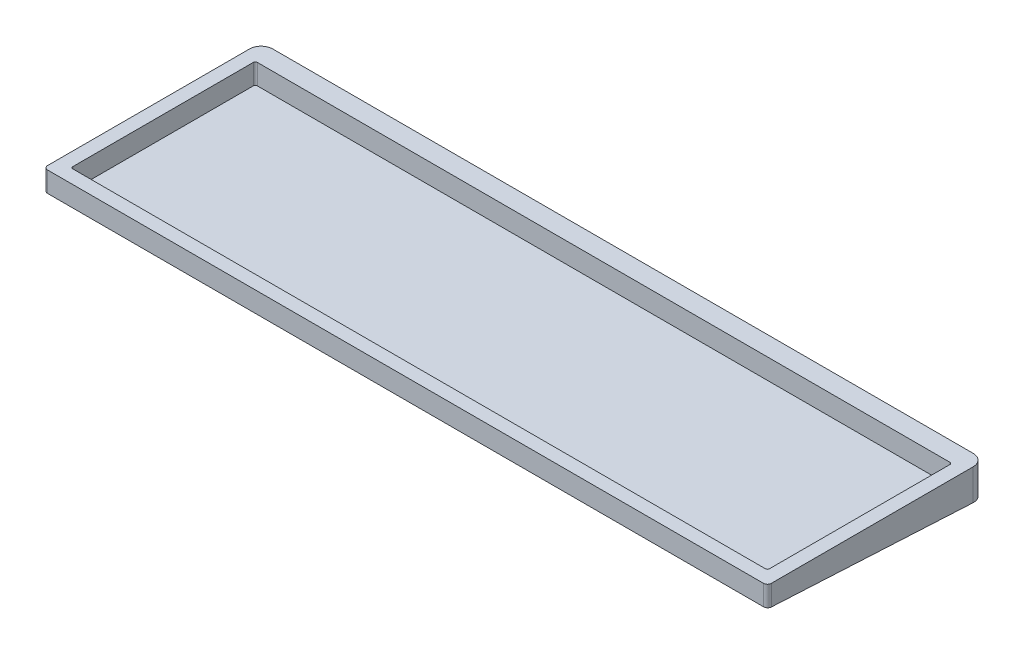
SolidWorks part; units mm, degrees
ref_plane "Front Plane" through (0, 0, 0) normal (0, 0, 1) x (1, 0, 0)
ref_plane "Top Plane" through (0, 0, 0) normal (0, 1, 0) x (1, 0, 0)
ref_plane "Right Plane" through (0, 0, 0) normal (1, 0, 0) x (0, 0, -1)
sketch "Sketch1" plane through (0, 0, 0) normal (0, 1, 0) x (1, 0, 0)
  line L1 (-178.825, 47.625) -> (178.825, 47.625)
  line L2 (-179.825, 46.625) -> (-179.825, -46.625)
  line L3 (-178.825, -47.625) -> (178.825, -47.625)
  line L4 (179.825, 46.625) -> (179.825, -46.625)
  line L5 (-179.825, 47.625) -> (179.825, -47.625) construction
  line L6 (-179.825, -47.625) -> (179.825, 47.625) construction
  arc A0 (178.825, -47.625) -> (179.825, -46.625) centre (178.825, -46.625) ccw
  arc A1 (178.825, 47.625) -> (179.825, 46.625) centre (178.825, 46.625) cw
  arc A2 (-179.825, -46.625) -> (-178.825, -47.625) centre (-178.825, -46.625) ccw
  arc A3 (-178.825, 47.625) -> (-179.825, 46.625) centre (-178.825, 46.625) ccw
  circle A4 centre (157.075, 19.175) radius 1.1
  circle A5 centre (136.925, -16.775) radius 1.1
  circle A6 centre (-153.475, 33.725) radius 1.1
  circle A7 centre (17.925, 22.275) radius 1.1
  circle A8 centre (17.875, -35.075) radius 1.1
  circle A9 centre (-130.375, -35.725) radius 1.1
  point P0 (0, 0)
  dimension "D3" = 1
  dimension "D4" = 2.2
  dimension "D7" = 2.2
  dimension "D8" = 2.2
  dimension "D9" = 2.2
  dimension "D10" = 2.2
  dimension "D11" = 2.2
  dimension "D1" = 359.65
  dimension "D2" = 95.25
  dimension "D5" = 22.75
  dimension "D6" = 28.45
  dimension "D12" = 42.9
  dimension "D13" = 30.85
  dimension "D14" = 25.35
  dimension "D15" = 161.9
  dimension "D16" = 12.55
  dimension "D17" = 161.95
  dimension "D18" = 11.9
  dimension "D19" = 49.45
  dimension "D20" = 13.9
  dimension "D21" = 26.35
sketch "Sketch2" plane through (0, 0, 0) normal (0, 1, 0) x (1, 0, 0)
  line L0 (-179.825, 46.625) -> (-179.825, -46.625) construction
  line L1 (-178.825, -47.625) -> (178.825, -47.625) construction
  line L2 (179.825, 46.625) -> (179.825, -46.625) construction
  line L3 (-178.825, 47.625) -> (178.825, 47.625) construction
  line L4 (-179.825, 46.625) -> (-179.825, -46.625)
  line L5 (-178.825, -47.625) -> (178.825, -47.625)
  line L6 (179.825, 46.625) -> (179.825, -46.625)
  line L7 (-178.825, 47.625) -> (178.825, 47.625)
  line L9 (-180.825, 57.625) -> (180.825, 57.625)
  line L10 (-186.825, 51.625) -> (-186.825, -52.625)
  line L11 (-184.825, -54.625) -> (184.825, -54.625)
  line L12 (186.825, 51.625) -> (186.825, -52.625)
  circle A0 centre (157.075, 19.175) radius 1.1 construction
  circle A1 centre (136.925, -16.775) radius 1.1 construction
  circle A2 centre (17.875, -35.075) radius 1.1 construction
  circle A3 centre (17.925, 22.275) radius 1.1 construction
  circle A4 centre (-153.475, 33.725) radius 1.1 construction
  circle A5 centre (-130.375, -35.725) radius 1.1 construction
  arc A6 (-179.825, -46.625) -> (-178.825, -47.625) centre (-178.825, -46.625) ccw construction
  arc A7 (178.825, -47.625) -> (179.825, -46.625) centre (178.825, -46.625) ccw construction
  arc A8 (179.825, 46.625) -> (178.825, 47.625) centre (178.825, 46.625) ccw construction
  arc A9 (-178.825, 47.625) -> (-179.825, 46.625) centre (-178.825, 46.625) ccw construction
  circle A10 centre (157.075, 19.175) radius 1.1
  circle A11 centre (136.925, -16.775) radius 1.1
  circle A12 centre (17.875, -35.075) radius 1.1
  circle A13 centre (17.925, 22.275) radius 1.1
  circle A14 centre (-153.475, 33.725) radius 1.1
  circle A15 centre (-130.375, -35.725) radius 1.1
  arc A16 (-179.825, -46.625) -> (-178.825, -47.625) centre (-178.825, -46.625) ccw
  arc A17 (178.825, -47.625) -> (179.825, -46.625) centre (178.825, -46.625) ccw
  arc A18 (179.825, 46.625) -> (178.825, 47.625) centre (178.825, 46.625) ccw
  arc A19 (-178.825, 47.625) -> (-179.825, 46.625) centre (-178.825, 46.625) ccw
  arc A20 (180.825, 57.625) -> (186.825, 51.625) centre (180.825, 51.625) cw
  arc A21 (-180.825, 57.625) -> (-186.825, 51.625) centre (-180.825, 51.625) ccw
  arc A22 (184.825, -54.625) -> (186.825, -52.625) centre (184.825, -52.625) ccw
  arc A23 (-186.825, -52.625) -> (-184.825, -54.625) centre (-184.825, -52.625) ccw
  point P30 (0, 0)
  dimension "D5" = 6
  dimension "D6" = 2
  dimension "D1" = 10
  dimension "D2" = 7
  dimension "D3" = 7
  dimension "D4" = 7
extrude "Boss-Extrude1" add sketch "Sketch2" along normal blind 10.5 contours L10 A23 L11 A22 L12 A20 L9 A21 A19 L7 A18 L6 A17 L5 A16 L4 region at (0, 0, -53.7235)
sketch "Sketch4" plane through (0, 0, 0) normal (0, -1, 0) x (1, 0, 0)
  line L0 (186.825, -51.625) -> (186.825, 52.625) construction
  line L1 (-180.825, -57.625) -> (180.825, -57.625) construction
  line L2 (-186.825, -51.625) -> (-186.825, 52.625) construction
  line L3 (-184.825, 54.625) -> (184.825, 54.625) construction
  line L4 (-179.825, 46.625) -> (-179.825, -46.625)
  line L5 (178.825, 47.625) -> (-178.825, 47.625)
  line L6 (179.825, -46.625) -> (179.825, 46.625)
  line L7 (-178.825, -47.625) -> (178.825, -47.625)
  line L8 (-179.825, 46.625) -> (-179.825, -46.625)
  line L10 (179.825, -46.625) -> (179.825, 46.625)
  line L11 (-178.825, -47.625) -> (178.825, -47.625)
  line L12 (186.825, -51.625) -> (186.825, 52.625)
  line L13 (-180.825, -57.625) -> (180.825, -57.625)
  line L14 (-186.825, -51.625) -> (-186.825, 52.625)
  line L15 (-184.825, 54.625) -> (184.825, 54.625)
  arc A0 (186.825, 52.625) -> (184.825, 54.625) centre (184.825, 52.625) ccw construction
  arc A1 (180.825, -57.625) -> (186.825, -51.625) centre (180.825, -51.625) ccw construction
  arc A2 (-186.825, -51.625) -> (-180.825, -57.625) centre (-180.825, -51.625) ccw construction
  arc A3 (-184.825, 54.625) -> (-186.825, 52.625) centre (-184.825, 52.625) ccw construction
  arc A4 (-179.825, -46.625) -> (-178.825, -47.625) centre (-178.825, -46.625) ccw
  arc A5 (-178.825, 47.625) -> (-179.825, 46.625) centre (-178.825, 46.625) ccw
  arc A6 (179.825, 46.625) -> (178.825, 47.625) centre (178.825, 46.625) ccw
  arc A7 (178.825, -47.625) -> (179.825, -46.625) centre (178.825, -46.625) ccw
  arc A8 (-179.825, -46.625) -> (-178.825, -47.625) centre (-178.825, -46.625) ccw
  arc A9 (-178.825, 47.625) -> (-179.825, 46.625) centre (-178.825, 46.625) ccw
  arc A10 (179.825, 46.625) -> (178.825, 47.625) centre (178.825, 46.625) ccw
  arc A11 (178.825, -47.625) -> (179.825, -46.625) centre (178.825, -46.625) ccw
  arc A12 (186.825, 52.625) -> (184.825, 54.625) centre (184.825, 52.625) ccw
  arc A13 (180.825, -57.625) -> (186.825, -51.625) centre (180.825, -51.625) ccw
  arc A14 (-186.825, -51.625) -> (-180.825, -57.625) centre (-180.825, -51.625) ccw
  arc A15 (-184.825, 54.625) -> (-186.825, 52.625) centre (-184.825, 52.625) ccw
  arc M9 (-178.825, -47.625) -> (-179.825, -46.625) centre (-178.825, -46.625) cw
  line M10 (-179.825, -46.625) -> (-179.825, 46.625)
  arc M11 (-179.825, 46.625) -> (-178.825, 47.625) centre (-178.825, 46.625) cw
  line M12 (-178.825, 47.625) -> (178.825, 47.625)
  arc M13 (178.825, 47.625) -> (179.825, 46.625) centre (178.825, 46.625) cw
  line M14 (179.825, 46.625) -> (179.825, -46.625)
  arc M15 (179.825, -46.625) -> (178.825, -47.625) centre (178.825, -46.625) cw
  line M16 (178.825, -47.625) -> (-178.825, -47.625)
  line M17 (-186.825, 52.625) -> (-186.825, -51.625)
  arc M18 (-186.825, -51.625) -> (-180.825, -57.625) centre (-180.825, -51.625) ccw
  line M19 (-180.825, -57.625) -> (180.825, -57.625)
  arc M20 (180.825, -57.625) -> (186.825, -51.625) centre (180.825, -51.625) ccw
  line M21 (186.825, -51.625) -> (186.825, 52.625)
  arc M22 (186.825, 52.625) -> (184.825, 54.625) centre (184.825, 52.625) ccw
  line M23 (184.825, 54.625) -> (-184.825, 54.625)
  arc M24 (-184.825, 54.625) -> (-186.825, 52.625) centre (-184.825, 52.625) ccw
  dimension "D1" = 0
extrude "Boss-Extrude3" add sketch "Sketch4" along normal blind 10.5 contours M24 M17 M18 M19 M20 M21 M22 M23 M16 M9 M10 M11 M12 M13 M14 M15 | M9 M16 M15 M14 M13 M12 M11 M10 region at (0, 0, 0) region at (182.3089, 0, -53.1089)
sketch "Sketch8" plane through (-186.825, 0, 0) normal (-1, 0, 0) x (0, 0, 1)
  line L0 (54.625, 0) -> (-57.625, 0) construction
  line L1 (54.625, 10.5) -> (54.625, -10.5) construction
  line L2 (-57.625, 10.5) -> (-57.625, -10.5) construction
  line L3 (54.625, 0) -> (-57.625, -5.8828)
  line L4 (-57.625, -5.8828) -> (-57.625, -10.5)
  line L5 (-57.625, -10.5) -> (54.625, -10.5)
  line L6 (54.625, -10.5) -> (54.625, 0)
  dimension "D1" = 87
extrude "Cut-Extrude4" cut sketch "Sketch8" against normal blind 400
sketch "Sketch9" plane through (0, 0, 0) normal (0, 1, 0) x (1, 0, 0)
  line L0 (-121.9453, 45.1) -> (-108.9453, 45.1)
  line L1 (-121.9453, 31.1) -> (-108.9453, 31.1)
  line L2 (-122.4453, 44.6) -> (-122.4453, 31.6)
  line L3 (-108.4453, 44.6) -> (-108.4453, 31.6)
  line L4 (-102.8953, 45.1) -> (-89.8953, 45.1)
  line L5 (-102.8953, 31.1) -> (-89.8953, 31.1)
  line L6 (-103.3953, 44.6) -> (-103.3953, 31.6)
  line L7 (-89.3953, 44.6) -> (-89.3953, 31.6)
  line L8 (-83.8453, 45.1) -> (-70.8453, 45.1)
  line L9 (-83.8453, 31.1) -> (-70.8453, 31.1)
  line L10 (-84.3453, 44.6) -> (-84.3453, 31.6)
  line L11 (-70.3453, 44.6) -> (-70.3453, 31.6)
  line L12 (-64.7953, 45.1) -> (-51.7953, 45.1)
  line L13 (-64.7953, 31.1) -> (-51.7953, 31.1)
  line L14 (-65.2953, 44.6) -> (-65.2953, 31.6)
  line L15 (-51.2953, 44.6) -> (-51.2953, 31.6)
  line L16 (-45.7453, 45.1) -> (-32.7453, 45.1)
  line L17 (-45.7453, 31.1) -> (-32.7453, 31.1)
  line L18 (-46.2453, 44.6) -> (-46.2453, 31.6)
  line L19 (-32.2453, 44.6) -> (-32.2453, 31.6)
  line L20 (-26.6953, 45.1) -> (-13.6953, 45.1)
  line L21 (-26.6953, 31.1) -> (-13.6953, 31.1)
  line L22 (-27.1953, 44.6) -> (-27.1953, 31.6)
  line L23 (-13.1953, 44.6) -> (-13.1953, 31.6)
  line L24 (-7.6453, 45.1) -> (5.3547, 45.1)
  line L25 (-7.6453, 31.1) -> (5.3547, 31.1)
  line L26 (-8.1453, 44.6) -> (-8.1453, 31.6)
  line L27 (5.8547, 44.6) -> (5.8547, 31.6)
  line L28 (11.4047, 45.1) -> (24.4047, 45.1)
  line L29 (11.4047, 31.1) -> (24.4047, 31.1)
  line L30 (10.9047, 44.6) -> (10.9047, 31.6)
  line L31 (24.9047, 44.6) -> (24.9047, 31.6)
  line L32 (30.4547, 45.1) -> (43.4547, 45.1)
  line L33 (30.4547, 31.1) -> (43.4547, 31.1)
  line L34 (29.9547, 44.6) -> (29.9547, 31.6)
  line L35 (43.9547, 44.6) -> (43.9547, 31.6)
  line L36 (49.5047, 45.1) -> (62.5047, 45.1)
  line L37 (49.5047, 31.1) -> (62.5047, 31.1)
  line L38 (49.0047, 44.6) -> (49.0047, 31.6)
  line L39 (63.0047, 44.6) -> (63.0047, 31.6)
  line L40 (68.5547, 45.1) -> (81.5547, 45.1)
  line L41 (68.5547, 31.1) -> (81.5547, 31.1)
  line L42 (68.0547, 44.6) -> (68.0547, 31.6)
  line L43 (82.0547, 44.6) -> (82.0547, 31.6)
  line L44 (87.6047, 45.1) -> (100.6047, 45.1)
  line L45 (87.6047, 31.1) -> (100.6047, 31.1)
  line L46 (87.1047, 44.6) -> (87.1047, 31.6)
  line L47 (101.1047, 44.6) -> (101.1047, 31.6)
  line L48 (106.6547, 45.1) -> (119.6547, 45.1)
  line L49 (106.6547, 31.1) -> (119.6547, 31.1)
  line L50 (106.1547, 44.6) -> (106.1547, 31.6)
  line L51 (120.1547, 44.6) -> (120.1547, 31.6)
  line L52 (135.2297, 45.1) -> (148.2297, 45.1)
  line L53 (135.2297, 31.1) -> (148.2297, 31.1)
  line L54 (134.7297, 44.6) -> (134.7297, 31.6)
  line L55 (148.7297, 44.6) -> (148.7297, 31.6)
  line L56 (150.6677, 44.1) -> (156.6677, 44.1)
  line L57 (150.6677, 29.1) -> (156.6677, 29.1)
  line L58 (150.1677, 43.6) -> (150.1677, 29.6)
  line L59 (157.1677, 43.6) -> (157.1677, 29.6)
  line L60 (126.7917, 44.1) -> (132.7917, 44.1)
  line L61 (126.7917, 29.1) -> (132.7917, 29.1)
  line L62 (126.2917, 43.6) -> (126.2917, 29.6)
  line L63 (133.2917, 43.6) -> (133.2917, 29.6)
  line L64 (163.8047, 45.1) -> (176.8047, 45.1)
  line L65 (163.8047, 31.1) -> (176.8047, 31.1)
  line L66 (163.3047, 44.6) -> (163.3047, 31.6)
  line L67 (177.3047, 44.6) -> (177.3047, 31.6)
  line L68 (-117.1828, 26.05) -> (-104.1828, 26.05)
  line L69 (-117.1828, 12.05) -> (-104.1828, 12.05)
  line L70 (-117.6828, 25.55) -> (-117.6828, 12.55)
  line L71 (-103.6828, 25.55) -> (-103.6828, 12.55)
  line L72 (-93.3703, 26.05) -> (-80.3703, 26.05)
  line L73 (-93.3703, 12.05) -> (-80.3703, 12.05)
  line L74 (-93.8703, 25.55) -> (-93.8703, 12.55)
  line L75 (-79.8703, 25.55) -> (-79.8703, 12.55)
  line L76 (-74.3203, 26.05) -> (-61.3203, 26.05)
  line L77 (-74.3203, 12.05) -> (-61.3203, 12.05)
  line L78 (-74.8203, 25.55) -> (-74.8203, 12.55)
  line L79 (-60.8203, 25.55) -> (-60.8203, 12.55)
  line L80 (-55.2703, 26.05) -> (-42.2703, 26.05)
  line L81 (-55.2703, 12.05) -> (-42.2703, 12.05)
  line L82 (-55.7703, 25.55) -> (-55.7703, 12.55)
  line L83 (-41.7703, 25.55) -> (-41.7703, 12.55)
  line L84 (-36.2203, 26.05) -> (-23.2203, 26.05)
  line L85 (-36.2203, 12.05) -> (-23.2203, 12.05)
  line L86 (-36.7203, 25.55) -> (-36.7203, 12.55)
  line L87 (-22.7203, 25.55) -> (-22.7203, 12.55)
  line L88 (-17.1703, 26.05) -> (-4.1703, 26.05)
  line L89 (-17.1703, 12.05) -> (-4.1703, 12.05)
  line L90 (-17.6703, 25.55) -> (-17.6703, 12.55)
  line L91 (-3.6703, 25.55) -> (-3.6703, 12.55)
  line L92 (1.8797, 26.05) -> (14.8797, 26.05)
  line L93 (1.8797, 12.05) -> (14.8797, 12.05)
  line L94 (1.3797, 25.55) -> (1.3797, 12.55)
  line L95 (15.3797, 25.55) -> (15.3797, 12.55)
  line L96 (20.9297, 26.05) -> (33.9297, 26.05)
  line L97 (20.9297, 12.05) -> (33.9297, 12.05)
  line L98 (20.4297, 25.55) -> (20.4297, 12.55)
  line L99 (34.4297, 25.55) -> (34.4297, 12.55)
  line L100 (39.9797, 26.05) -> (52.9797, 26.05)
  line L101 (39.9797, 12.05) -> (52.9797, 12.05)
  line L102 (39.4797, 25.55) -> (39.4797, 12.55)
  line L103 (53.4797, 25.55) -> (53.4797, 12.55)
  line L104 (59.0297, 26.05) -> (72.0297, 26.05)
  line L105 (59.0297, 12.05) -> (72.0297, 12.05)
  line L106 (58.5297, 25.55) -> (58.5297, 12.55)
  line L107 (72.5297, 25.55) -> (72.5297, 12.55)
  line L108 (78.0797, 26.05) -> (91.0797, 26.05)
  line L109 (78.0797, 12.05) -> (91.0797, 12.05)
  line L110 (77.5797, 25.55) -> (77.5797, 12.55)
  line L111 (91.5797, 25.55) -> (91.5797, 12.55)
  line L112 (97.1297, 26.05) -> (110.1297, 26.05)
  line L113 (97.1297, 12.05) -> (110.1297, 12.05)
  line L114 (96.6297, 25.55) -> (96.6297, 12.55)
  line L115 (110.6297, 25.55) -> (110.6297, 12.55)
  line L116 (116.1797, 26.05) -> (129.1797, 26.05)
  line L117 (116.1797, 12.05) -> (129.1797, 12.05)
  line L118 (115.6797, 25.55) -> (115.6797, 12.55)
  line L119 (129.6797, 25.55) -> (129.6797, 12.55)
  line L120 (139.9922, 26.05) -> (152.9922, 26.05)
  line L121 (139.9922, 12.05) -> (152.9922, 12.05)
  line L122 (139.4922, 25.55) -> (139.4922, 12.55)
  line L123 (153.4922, 25.55) -> (153.4922, 12.55)
  line L124 (163.8047, 26.05) -> (176.8047, 26.05)
  line L125 (163.8047, 12.05) -> (176.8047, 12.05)
  line L126 (163.3047, 25.55) -> (163.3047, 12.55)
  line L127 (177.3047, 25.55) -> (177.3047, 12.55)
  line L128 (-114.8016, 7) -> (-101.8016, 7)
  line L129 (-114.8016, -7) -> (-101.8016, -7)
  line L130 (-115.3016, 6.5) -> (-115.3016, -6.5)
  line L131 (-101.3016, 6.5) -> (-101.3016, -6.5)
  line L132 (-88.6078, 7) -> (-75.6078, 7)
  line L133 (-88.6078, -7) -> (-75.6078, -7)
  line L134 (-89.1078, 6.5) -> (-89.1078, -6.5)
  line L135 (-75.1078, 6.5) -> (-75.1078, -6.5)
  line L136 (-69.5578, 7) -> (-56.5578, 7)
  line L137 (-69.5578, -7) -> (-56.5578, -7)
  line L138 (-70.0578, 6.5) -> (-70.0578, -6.5)
  line L139 (-56.0578, 6.5) -> (-56.0578, -6.5)
  line L140 (-50.5078, 7) -> (-37.5078, 7)
  line L141 (-50.5078, -7) -> (-37.5078, -7)
  line L142 (-51.0078, 6.5) -> (-51.0078, -6.5)
  line L143 (-37.0078, 6.5) -> (-37.0078, -6.5)
  line L144 (-31.4578, 7) -> (-18.4578, 7)
  line L145 (-31.4578, -7) -> (-18.4578, -7)
  line L146 (-31.9578, 6.5) -> (-31.9578, -6.5)
  line L147 (-17.9578, 6.5) -> (-17.9578, -6.5)
  line L148 (-12.4078, 7) -> (0.5922, 7)
  line L149 (-12.4078, -7) -> (0.5922, -7)
  line L150 (-12.9078, 6.5) -> (-12.9078, -6.5)
  line L151 (1.0922, 6.5) -> (1.0922, -6.5)
  line L152 (6.6422, 7) -> (19.6422, 7)
  line L153 (6.6422, -7) -> (19.6422, -7)
  line L154 (6.1422, 6.5) -> (6.1422, -6.5)
  line L155 (20.1422, 6.5) -> (20.1422, -6.5)
  line L156 (25.6922, 7) -> (38.6922, 7)
  line L157 (25.6922, -7) -> (38.6922, -7)
  line L158 (25.1922, 6.5) -> (25.1922, -6.5)
  line L159 (39.1922, 6.5) -> (39.1922, -6.5)
  line L160 (44.7422, 7) -> (57.7422, 7)
  line L161 (44.7422, -7) -> (57.7422, -7)
  line L162 (44.2422, 6.5) -> (44.2422, -6.5)
  line L163 (58.2422, 6.5) -> (58.2422, -6.5)
  line L164 (63.7922, 7) -> (76.7922, 7)
  line L165 (63.7922, -7) -> (76.7922, -7)
  line L166 (63.2922, 6.5) -> (63.2922, -6.5)
  line L167 (77.2922, 6.5) -> (77.2922, -6.5)
  line L168 (82.8422, 7) -> (95.8422, 7)
  line L169 (82.8422, -7) -> (95.8422, -7)
  line L170 (82.3422, 6.5) -> (82.3422, -6.5)
  line L171 (96.3422, 6.5) -> (96.3422, -6.5)
  line L172 (101.8922, 7) -> (114.8922, 7)
  line L173 (101.8922, -7) -> (114.8922, -7)
  line L174 (101.3922, 6.5) -> (101.3922, -6.5)
  line L175 (115.3922, 6.5) -> (115.3922, -6.5)
  line L176 (132.8484, 7) -> (145.8484, 7)
  line L177 (132.8484, -7) -> (145.8484, -7)
  line L178 (132.3484, 6.5) -> (132.3484, -6.5)
  line L179 (146.3484, 6.5) -> (146.3484, -6.5)
  line L180 (148.2864, 6) -> (154.2864, 6)
  line L181 (148.2864, -9) -> (154.2864, -9)
  line L182 (147.7864, 5.5) -> (147.7864, -8.5)
  line L183 (154.7864, 5.5) -> (154.7864, -8.5)
  line L184 (124.4104, 6) -> (130.4104, 6)
  line L185 (124.4104, -9) -> (130.4104, -9)
  line L186 (123.9104, 5.5) -> (123.9104, -8.5)
  line L187 (130.9104, 5.5) -> (130.9104, -8.5)
  line L188 (163.8047, 7) -> (176.8047, 7)
  line L189 (163.8047, -7) -> (176.8047, -7)
  line L190 (163.3047, 6.5) -> (163.3047, -6.5)
  line L191 (177.3047, 6.5) -> (177.3047, -6.5)
  line L192 (-110.0391, -12.05) -> (-97.0391, -12.05)
  line L193 (-110.0391, -26.05) -> (-97.0391, -26.05)
  line L194 (-110.5391, -12.55) -> (-110.5391, -25.55)
  line L195 (-96.5391, -12.55) -> (-96.5391, -25.55)
  line L196 (-94.6011, -13.05) -> (-88.6011, -13.05)
  line L197 (-94.6011, -28.05) -> (-88.6011, -28.05)
  line L198 (-95.1011, -13.55) -> (-95.1011, -27.55)
  line L199 (-88.1011, -13.55) -> (-88.1011, -27.55)
  line L200 (-118.4771, -13.05) -> (-112.4771, -13.05)
  line L201 (-118.4771, -28.05) -> (-112.4771, -28.05)
  line L202 (-118.9771, -13.55) -> (-118.9771, -27.55)
  line L203 (-111.9771, -13.55) -> (-111.9771, -27.55)
  line L204 (-79.0828, -12.05) -> (-66.0828, -12.05)
  line L205 (-79.0828, -26.05) -> (-66.0828, -26.05)
  line L206 (-79.5828, -12.55) -> (-79.5828, -25.55)
  line L207 (-65.5828, -12.55) -> (-65.5828, -25.55)
  line L208 (-60.0328, -12.05) -> (-47.0328, -12.05)
  line L209 (-60.0328, -26.05) -> (-47.0328, -26.05)
  line L210 (-60.5328, -12.55) -> (-60.5328, -25.55)
  line L211 (-46.5328, -12.55) -> (-46.5328, -25.55)
  line L212 (-40.9828, -12.05) -> (-27.9828, -12.05)
  line L213 (-40.9828, -26.05) -> (-27.9828, -26.05)
  line L214 (-41.4828, -12.55) -> (-41.4828, -25.55)
  line L215 (-27.4828, -12.55) -> (-27.4828, -25.55)
  line L216 (-21.9328, -12.05) -> (-8.9328, -12.05)
  line L217 (-21.9328, -26.05) -> (-8.9328, -26.05)
  line L218 (-22.4328, -12.55) -> (-22.4328, -25.55)
  line L219 (-8.4328, -12.55) -> (-8.4328, -25.55)
  line L220 (-2.8828, -12.05) -> (10.1172, -12.05)
  line L221 (-2.8828, -26.05) -> (10.1172, -26.05)
  line L222 (-3.3828, -12.55) -> (-3.3828, -25.55)
  line L223 (10.6172, -12.55) -> (10.6172, -25.55)
  line L224 (16.1672, -12.05) -> (29.1672, -12.05)
  line L225 (16.1672, -26.05) -> (29.1672, -26.05)
  line L226 (15.6672, -12.55) -> (15.6672, -25.55)
  line L227 (29.6672, -12.55) -> (29.6672, -25.55)
  line L228 (35.2172, -12.05) -> (48.2172, -12.05)
  line L229 (35.2172, -26.05) -> (48.2172, -26.05)
  line L230 (34.7172, -12.55) -> (34.7172, -25.55)
  line L231 (48.7172, -12.55) -> (48.7172, -25.55)
  line L232 (54.2672, -12.05) -> (67.2672, -12.05)
  line L233 (54.2672, -26.05) -> (67.2672, -26.05)
  line L234 (53.7672, -12.55) -> (53.7672, -25.55)
  line L235 (67.7672, -12.55) -> (67.7672, -25.55)
  line L236 (73.3172, -12.05) -> (86.3172, -12.05)
  line L237 (73.3172, -26.05) -> (86.3172, -26.05)
  line L238 (72.8172, -12.55) -> (72.8172, -25.55)
  line L239 (86.8172, -12.55) -> (86.8172, -25.55)
  line L240 (92.3672, -12.05) -> (105.3672, -12.05)
  line L241 (92.3672, -26.05) -> (105.3672, -26.05)
  line L242 (91.8672, -12.55) -> (91.8672, -25.55)
  line L243 (105.8672, -12.55) -> (105.8672, -25.55)
  line L244 (118.5609, -12.05) -> (131.5609, -12.05)
  line L245 (118.5609, -26.05) -> (131.5609, -26.05)
  line L246 (118.0609, -12.55) -> (118.0609, -25.55)
  line L247 (132.0609, -12.55) -> (132.0609, -25.55)
  line L248 (144.7547, -12.05) -> (157.7547, -12.05)
  line L249 (144.7547, -26.05) -> (157.7547, -26.05)
  line L250 (144.2547, -12.55) -> (144.2547, -25.55)
  line L251 (158.2547, -12.55) -> (158.2547, -25.55)
  line L252 (163.8047, -12.05) -> (176.8047, -12.05)
  line L253 (163.8047, -26.05) -> (176.8047, -26.05)
  line L254 (163.3047, -12.55) -> (163.3047, -25.55)
  line L255 (177.3047, -12.55) -> (177.3047, -25.55)
  line L256 (-119.5641, -31.1) -> (-106.5641, -31.1)
  line L257 (-119.5641, -45.1) -> (-106.5641, -45.1)
  line L258 (-120.0641, -31.6) -> (-120.0641, -44.6)
  line L259 (-106.0641, -31.6) -> (-106.0641, -44.6)
  line L260 (-95.7516, -31.1) -> (-82.7516, -31.1)
  line L261 (-95.7516, -45.1) -> (-82.7516, -45.1)
  line L262 (-96.2516, -31.6) -> (-96.2516, -44.6)
  line L263 (-82.2516, -31.6) -> (-82.2516, -44.6)
  line L264 (-71.9391, -31.1) -> (-58.9391, -31.1)
  line L265 (-71.9391, -45.1) -> (-58.9391, -45.1)
  line L266 (-72.4391, -31.6) -> (-72.4391, -44.6)
  line L267 (-58.4391, -31.6) -> (-58.4391, -44.6)
  line L268 (-0.5016, -31.1) -> (12.4984, -31.1)
  line L269 (-0.5016, -45.1) -> (12.4984, -45.1)
  line L270 (-1.0016, -31.6) -> (-1.0016, -44.6)
  line L271 (12.9984, -31.6) -> (12.9984, -44.6)
  line L272 (52.9984, -32.1) -> (58.9984, -32.1)
  line L273 (52.9984, -47.1) -> (58.9984, -47.1)
  line L274 (52.4984, -32.6) -> (52.4984, -46.6)
  line L275 (59.4984, -32.6) -> (59.4984, -46.6)
  line L276 (-47.0016, -32.1) -> (-41.0016, -32.1)
  line L277 (-47.0016, -47.1) -> (-41.0016, -47.1)
  line L278 (-47.5016, -32.6) -> (-47.5016, -46.6)
  line L279 (-40.5016, -32.6) -> (-40.5016, -46.6)
  line L280 (68.5547, -31.1) -> (81.5547, -31.1)
  line L281 (68.5547, -45.1) -> (81.5547, -45.1)
  line L282 (68.0547, -31.6) -> (68.0547, -44.6)
  line L283 (82.0547, -31.6) -> (82.0547, -44.6)
  line L284 (87.6047, -31.1) -> (100.6047, -31.1)
  line L285 (87.6047, -45.1) -> (100.6047, -45.1)
  line L286 (87.1047, -31.6) -> (87.1047, -44.6)
  line L287 (101.1047, -31.6) -> (101.1047, -44.6)
  line L288 (106.6547, -31.1) -> (119.6547, -31.1)
  line L289 (106.6547, -45.1) -> (119.6547, -45.1)
  line L290 (106.1547, -31.6) -> (106.1547, -44.6)
  line L291 (120.1547, -31.6) -> (120.1547, -44.6)
  line L292 (125.7047, -31.1) -> (138.7047, -31.1)
  line L293 (125.7047, -45.1) -> (138.7047, -45.1)
  line L294 (125.2047, -31.6) -> (125.2047, -44.6)
  line L295 (139.2047, -31.6) -> (139.2047, -44.6)
  line L296 (144.7547, -31.1) -> (157.7547, -31.1)
  line L297 (144.7547, -45.1) -> (157.7547, -45.1)
  line L298 (144.2547, -31.6) -> (144.2547, -44.6)
  line L299 (158.2547, -31.6) -> (158.2547, -44.6)
  line L300 (163.8047, -31.1) -> (176.8047, -31.1)
  line L301 (163.8047, -45.1) -> (176.8047, -45.1)
  line L302 (163.3047, -31.6) -> (163.3047, -44.6)
  line L303 (177.3047, -31.6) -> (177.3047, -44.6)
  line L304 (-124.9703, 47.625) -> (179.8297, 47.625)
  line L305 (-124.9703, -47.625) -> (179.8297, -47.625)
  line L306 (-124.9703, 47.625) -> (-124.9703, -47.625)
  line L307 (179.8297, 47.625) -> (179.8297, -47.625)
  arc A0 (-121.9453, 45.1) -> (-122.4453, 44.6) centre (-121.9453, 44.6) ccw
  arc A1 (-108.4453, 44.6) -> (-108.9453, 45.1) centre (-108.9453, 44.6) ccw
  arc A2 (-122.4453, 31.6) -> (-121.9453, 31.1) centre (-121.9453, 31.6) ccw
  arc A3 (-108.9453, 31.1) -> (-108.4453, 31.6) centre (-108.9453, 31.6) ccw
  arc A4 (-102.8953, 45.1) -> (-103.3953, 44.6) centre (-102.8953, 44.6) ccw
  arc A5 (-89.3953, 44.6) -> (-89.8953, 45.1) centre (-89.8953, 44.6) ccw
  arc A6 (-103.3953, 31.6) -> (-102.8953, 31.1) centre (-102.8953, 31.6) ccw
  arc A7 (-89.8953, 31.1) -> (-89.3953, 31.6) centre (-89.8953, 31.6) ccw
  arc A8 (-83.8453, 45.1) -> (-84.3453, 44.6) centre (-83.8453, 44.6) ccw
  arc A9 (-70.3453, 44.6) -> (-70.8453, 45.1) centre (-70.8453, 44.6) ccw
  arc A10 (-84.3453, 31.6) -> (-83.8453, 31.1) centre (-83.8453, 31.6) ccw
  arc A11 (-70.8453, 31.1) -> (-70.3453, 31.6) centre (-70.8453, 31.6) ccw
  arc A12 (-64.7953, 45.1) -> (-65.2953, 44.6) centre (-64.7953, 44.6) ccw
  arc A13 (-51.2953, 44.6) -> (-51.7953, 45.1) centre (-51.7953, 44.6) ccw
  arc A14 (-65.2953, 31.6) -> (-64.7953, 31.1) centre (-64.7953, 31.6) ccw
  arc A15 (-51.7953, 31.1) -> (-51.2953, 31.6) centre (-51.7953, 31.6) ccw
  arc A16 (-45.7453, 45.1) -> (-46.2453, 44.6) centre (-45.7453, 44.6) ccw
  arc A17 (-32.2453, 44.6) -> (-32.7453, 45.1) centre (-32.7453, 44.6) ccw
  arc A18 (-46.2453, 31.6) -> (-45.7453, 31.1) centre (-45.7453, 31.6) ccw
  arc A19 (-32.7453, 31.1) -> (-32.2453, 31.6) centre (-32.7453, 31.6) ccw
  arc A20 (-26.6953, 45.1) -> (-27.1953, 44.6) centre (-26.6953, 44.6) ccw
  arc A21 (-13.1953, 44.6) -> (-13.6953, 45.1) centre (-13.6953, 44.6) ccw
  arc A22 (-27.1953, 31.6) -> (-26.6953, 31.1) centre (-26.6953, 31.6) ccw
  arc A23 (-13.6953, 31.1) -> (-13.1953, 31.6) centre (-13.6953, 31.6) ccw
  arc A24 (-7.6453, 45.1) -> (-8.1453, 44.6) centre (-7.6453, 44.6) ccw
  arc A25 (5.8547, 44.6) -> (5.3547, 45.1) centre (5.3547, 44.6) ccw
  arc A26 (-8.1453, 31.6) -> (-7.6453, 31.1) centre (-7.6453, 31.6) ccw
  arc A27 (5.3547, 31.1) -> (5.8547, 31.6) centre (5.3547, 31.6) ccw
  arc A28 (11.4047, 45.1) -> (10.9047, 44.6) centre (11.4047, 44.6) ccw
  arc A29 (24.9047, 44.6) -> (24.4047, 45.1) centre (24.4047, 44.6) ccw
  arc A30 (10.9047, 31.6) -> (11.4047, 31.1) centre (11.4047, 31.6) ccw
  arc A31 (24.4047, 31.1) -> (24.9047, 31.6) centre (24.4047, 31.6) ccw
  arc A32 (30.4547, 45.1) -> (29.9547, 44.6) centre (30.4547, 44.6) ccw
  arc A33 (43.9547, 44.6) -> (43.4547, 45.1) centre (43.4547, 44.6) ccw
  arc A34 (29.9547, 31.6) -> (30.4547, 31.1) centre (30.4547, 31.6) ccw
  arc A35 (43.4547, 31.1) -> (43.9547, 31.6) centre (43.4547, 31.6) ccw
  arc A36 (49.5047, 45.1) -> (49.0047, 44.6) centre (49.5047, 44.6) ccw
  arc A37 (63.0047, 44.6) -> (62.5047, 45.1) centre (62.5047, 44.6) ccw
  arc A38 (49.0047, 31.6) -> (49.5047, 31.1) centre (49.5047, 31.6) ccw
  arc A39 (62.5047, 31.1) -> (63.0047, 31.6) centre (62.5047, 31.6) ccw
  arc A40 (68.5547, 45.1) -> (68.0547, 44.6) centre (68.5547, 44.6) ccw
  arc A41 (82.0547, 44.6) -> (81.5547, 45.1) centre (81.5547, 44.6) ccw
  arc A42 (68.0547, 31.6) -> (68.5547, 31.1) centre (68.5547, 31.6) ccw
  arc A43 (81.5547, 31.1) -> (82.0547, 31.6) centre (81.5547, 31.6) ccw
  arc A44 (87.6047, 45.1) -> (87.1047, 44.6) centre (87.6047, 44.6) ccw
  arc A45 (101.1047, 44.6) -> (100.6047, 45.1) centre (100.6047, 44.6) ccw
  arc A46 (87.1047, 31.6) -> (87.6047, 31.1) centre (87.6047, 31.6) ccw
  arc A47 (100.6047, 31.1) -> (101.1047, 31.6) centre (100.6047, 31.6) ccw
  arc A48 (106.6547, 45.1) -> (106.1547, 44.6) centre (106.6547, 44.6) ccw
  arc A49 (120.1547, 44.6) -> (119.6547, 45.1) centre (119.6547, 44.6) ccw
  arc A50 (106.1547, 31.6) -> (106.6547, 31.1) centre (106.6547, 31.6) ccw
  arc A51 (119.6547, 31.1) -> (120.1547, 31.6) centre (119.6547, 31.6) ccw
  arc A52 (135.2297, 45.1) -> (134.7297, 44.6) centre (135.2297, 44.6) ccw
  arc A53 (148.7297, 44.6) -> (148.2297, 45.1) centre (148.2297, 44.6) ccw
  arc A54 (134.7297, 31.6) -> (135.2297, 31.1) centre (135.2297, 31.6) ccw
  arc A55 (148.2297, 31.1) -> (148.7297, 31.6) centre (148.2297, 31.6) ccw
  arc A56 (150.6677, 44.1) -> (150.1677, 43.6) centre (150.6677, 43.6) ccw
  arc A57 (157.1677, 43.6) -> (156.6677, 44.1) centre (156.6677, 43.6) ccw
  arc A58 (150.1677, 29.6) -> (150.6677, 29.1) centre (150.6677, 29.6) ccw
  arc A59 (156.6677, 29.1) -> (157.1677, 29.6) centre (156.6677, 29.6) ccw
  arc A60 (126.7917, 44.1) -> (126.2917, 43.6) centre (126.7917, 43.6) ccw
  arc A61 (133.2917, 43.6) -> (132.7917, 44.1) centre (132.7917, 43.6) ccw
  arc A62 (126.2917, 29.6) -> (126.7917, 29.1) centre (126.7917, 29.6) ccw
  arc A63 (132.7917, 29.1) -> (133.2917, 29.6) centre (132.7917, 29.6) ccw
  arc A64 (163.8047, 45.1) -> (163.3047, 44.6) centre (163.8047, 44.6) ccw
  arc A65 (177.3047, 44.6) -> (176.8047, 45.1) centre (176.8047, 44.6) ccw
  arc A66 (163.3047, 31.6) -> (163.8047, 31.1) centre (163.8047, 31.6) ccw
  arc A67 (176.8047, 31.1) -> (177.3047, 31.6) centre (176.8047, 31.6) ccw
  arc A68 (-117.1828, 26.05) -> (-117.6828, 25.55) centre (-117.1828, 25.55) ccw
  arc A69 (-103.6828, 25.55) -> (-104.1828, 26.05) centre (-104.1828, 25.55) ccw
  arc A70 (-117.6828, 12.55) -> (-117.1828, 12.05) centre (-117.1828, 12.55) ccw
  arc A71 (-104.1828, 12.05) -> (-103.6828, 12.55) centre (-104.1828, 12.55) ccw
  arc A72 (-93.3703, 26.05) -> (-93.8703, 25.55) centre (-93.3703, 25.55) ccw
  arc A73 (-79.8703, 25.55) -> (-80.3703, 26.05) centre (-80.3703, 25.55) ccw
  arc A74 (-93.8703, 12.55) -> (-93.3703, 12.05) centre (-93.3703, 12.55) ccw
  arc A75 (-80.3703, 12.05) -> (-79.8703, 12.55) centre (-80.3703, 12.55) ccw
  arc A76 (-74.3203, 26.05) -> (-74.8203, 25.55) centre (-74.3203, 25.55) ccw
  arc A77 (-60.8203, 25.55) -> (-61.3203, 26.05) centre (-61.3203, 25.55) ccw
  arc A78 (-74.8203, 12.55) -> (-74.3203, 12.05) centre (-74.3203, 12.55) ccw
  arc A79 (-61.3203, 12.05) -> (-60.8203, 12.55) centre (-61.3203, 12.55) ccw
  arc A80 (-55.2703, 26.05) -> (-55.7703, 25.55) centre (-55.2703, 25.55) ccw
  arc A81 (-41.7703, 25.55) -> (-42.2703, 26.05) centre (-42.2703, 25.55) ccw
  arc A82 (-55.7703, 12.55) -> (-55.2703, 12.05) centre (-55.2703, 12.55) ccw
  arc A83 (-42.2703, 12.05) -> (-41.7703, 12.55) centre (-42.2703, 12.55) ccw
  arc A84 (-36.2203, 26.05) -> (-36.7203, 25.55) centre (-36.2203, 25.55) ccw
  arc A85 (-22.7203, 25.55) -> (-23.2203, 26.05) centre (-23.2203, 25.55) ccw
  arc A86 (-36.7203, 12.55) -> (-36.2203, 12.05) centre (-36.2203, 12.55) ccw
  arc A87 (-23.2203, 12.05) -> (-22.7203, 12.55) centre (-23.2203, 12.55) ccw
  arc A88 (-17.1703, 26.05) -> (-17.6703, 25.55) centre (-17.1703, 25.55) ccw
  arc A89 (-3.6703, 25.55) -> (-4.1703, 26.05) centre (-4.1703, 25.55) ccw
  arc A90 (-17.6703, 12.55) -> (-17.1703, 12.05) centre (-17.1703, 12.55) ccw
  arc A91 (-4.1703, 12.05) -> (-3.6703, 12.55) centre (-4.1703, 12.55) ccw
  arc A92 (1.8797, 26.05) -> (1.3797, 25.55) centre (1.8797, 25.55) ccw
  arc A93 (15.3797, 25.55) -> (14.8797, 26.05) centre (14.8797, 25.55) ccw
  arc A94 (1.3797, 12.55) -> (1.8797, 12.05) centre (1.8797, 12.55) ccw
  arc A95 (14.8797, 12.05) -> (15.3797, 12.55) centre (14.8797, 12.55) ccw
  arc A96 (20.9297, 26.05) -> (20.4297, 25.55) centre (20.9297, 25.55) ccw
  arc A97 (34.4297, 25.55) -> (33.9297, 26.05) centre (33.9297, 25.55) ccw
  arc A98 (20.4297, 12.55) -> (20.9297, 12.05) centre (20.9297, 12.55) ccw
  arc A99 (33.9297, 12.05) -> (34.4297, 12.55) centre (33.9297, 12.55) ccw
  arc A100 (39.9797, 26.05) -> (39.4797, 25.55) centre (39.9797, 25.55) ccw
  arc A101 (53.4797, 25.55) -> (52.9797, 26.05) centre (52.9797, 25.55) ccw
  arc A102 (39.4797, 12.55) -> (39.9797, 12.05) centre (39.9797, 12.55) ccw
  arc A103 (52.9797, 12.05) -> (53.4797, 12.55) centre (52.9797, 12.55) ccw
  arc A104 (59.0297, 26.05) -> (58.5297, 25.55) centre (59.0297, 25.55) ccw
  arc A105 (72.5297, 25.55) -> (72.0297, 26.05) centre (72.0297, 25.55) ccw
  arc A106 (58.5297, 12.55) -> (59.0297, 12.05) centre (59.0297, 12.55) ccw
  arc A107 (72.0297, 12.05) -> (72.5297, 12.55) centre (72.0297, 12.55) ccw
  arc A108 (78.0797, 26.05) -> (77.5797, 25.55) centre (78.0797, 25.55) ccw
  arc A109 (91.5797, 25.55) -> (91.0797, 26.05) centre (91.0797, 25.55) ccw
  arc A110 (77.5797, 12.55) -> (78.0797, 12.05) centre (78.0797, 12.55) ccw
  arc A111 (91.0797, 12.05) -> (91.5797, 12.55) centre (91.0797, 12.55) ccw
  arc A112 (97.1297, 26.05) -> (96.6297, 25.55) centre (97.1297, 25.55) ccw
  arc A113 (110.6297, 25.55) -> (110.1297, 26.05) centre (110.1297, 25.55) ccw
  arc A114 (96.6297, 12.55) -> (97.1297, 12.05) centre (97.1297, 12.55) ccw
  arc A115 (110.1297, 12.05) -> (110.6297, 12.55) centre (110.1297, 12.55) ccw
  arc A116 (116.1797, 26.05) -> (115.6797, 25.55) centre (116.1797, 25.55) ccw
  arc A117 (129.6797, 25.55) -> (129.1797, 26.05) centre (129.1797, 25.55) ccw
  arc A118 (115.6797, 12.55) -> (116.1797, 12.05) centre (116.1797, 12.55) ccw
  arc A119 (129.1797, 12.05) -> (129.6797, 12.55) centre (129.1797, 12.55) ccw
  arc A120 (139.9922, 26.05) -> (139.4922, 25.55) centre (139.9922, 25.55) ccw
  arc A121 (153.4922, 25.55) -> (152.9922, 26.05) centre (152.9922, 25.55) ccw
  arc A122 (139.4922, 12.55) -> (139.9922, 12.05) centre (139.9922, 12.55) ccw
  arc A123 (152.9922, 12.05) -> (153.4922, 12.55) centre (152.9922, 12.55) ccw
  arc A124 (163.8047, 26.05) -> (163.3047, 25.55) centre (163.8047, 25.55) ccw
  arc A125 (177.3047, 25.55) -> (176.8047, 26.05) centre (176.8047, 25.55) ccw
  arc A126 (163.3047, 12.55) -> (163.8047, 12.05) centre (163.8047, 12.55) ccw
  arc A127 (176.8047, 12.05) -> (177.3047, 12.55) centre (176.8047, 12.55) ccw
  arc A128 (-114.8016, 7) -> (-115.3016, 6.5) centre (-114.8016, 6.5) ccw
  arc A129 (-101.3016, 6.5) -> (-101.8016, 7) centre (-101.8016, 6.5) ccw
  arc A130 (-115.3016, -6.5) -> (-114.8016, -7) centre (-114.8016, -6.5) ccw
  arc A131 (-101.8016, -7) -> (-101.3016, -6.5) centre (-101.8016, -6.5) ccw
  arc A132 (-88.6078, 7) -> (-89.1078, 6.5) centre (-88.6078, 6.5) ccw
  arc A133 (-75.1078, 6.5) -> (-75.6078, 7) centre (-75.6078, 6.5) ccw
  arc A134 (-89.1078, -6.5) -> (-88.6078, -7) centre (-88.6078, -6.5) ccw
  arc A135 (-75.6078, -7) -> (-75.1078, -6.5) centre (-75.6078, -6.5) ccw
  arc A136 (-69.5578, 7) -> (-70.0578, 6.5) centre (-69.5578, 6.5) ccw
  arc A137 (-56.0578, 6.5) -> (-56.5578, 7) centre (-56.5578, 6.5) ccw
  arc A138 (-70.0578, -6.5) -> (-69.5578, -7) centre (-69.5578, -6.5) ccw
  arc A139 (-56.5578, -7) -> (-56.0578, -6.5) centre (-56.5578, -6.5) ccw
  arc A140 (-50.5078, 7) -> (-51.0078, 6.5) centre (-50.5078, 6.5) ccw
  arc A141 (-37.0078, 6.5) -> (-37.5078, 7) centre (-37.5078, 6.5) ccw
  arc A142 (-51.0078, -6.5) -> (-50.5078, -7) centre (-50.5078, -6.5) ccw
  arc A143 (-37.5078, -7) -> (-37.0078, -6.5) centre (-37.5078, -6.5) ccw
  arc A144 (-31.4578, 7) -> (-31.9578, 6.5) centre (-31.4578, 6.5) ccw
  arc A145 (-17.9578, 6.5) -> (-18.4578, 7) centre (-18.4578, 6.5) ccw
  arc A146 (-31.9578, -6.5) -> (-31.4578, -7) centre (-31.4578, -6.5) ccw
  arc A147 (-18.4578, -7) -> (-17.9578, -6.5) centre (-18.4578, -6.5) ccw
  arc A148 (-12.4078, 7) -> (-12.9078, 6.5) centre (-12.4078, 6.5) ccw
  arc A149 (1.0922, 6.5) -> (0.5922, 7) centre (0.5922, 6.5) ccw
  arc A150 (-12.9078, -6.5) -> (-12.4078, -7) centre (-12.4078, -6.5) ccw
  arc A151 (0.5922, -7) -> (1.0922, -6.5) centre (0.5922, -6.5) ccw
  arc A152 (6.6422, 7) -> (6.1422, 6.5) centre (6.6422, 6.5) ccw
  arc A153 (20.1422, 6.5) -> (19.6422, 7) centre (19.6422, 6.5) ccw
  arc A154 (6.1422, -6.5) -> (6.6422, -7) centre (6.6422, -6.5) ccw
  arc A155 (19.6422, -7) -> (20.1422, -6.5) centre (19.6422, -6.5) ccw
  arc A156 (25.6922, 7) -> (25.1922, 6.5) centre (25.6922, 6.5) ccw
  arc A157 (39.1922, 6.5) -> (38.6922, 7) centre (38.6922, 6.5) ccw
  arc A158 (25.1922, -6.5) -> (25.6922, -7) centre (25.6922, -6.5) ccw
  arc A159 (38.6922, -7) -> (39.1922, -6.5) centre (38.6922, -6.5) ccw
  arc A160 (44.7422, 7) -> (44.2422, 6.5) centre (44.7422, 6.5) ccw
  arc A161 (58.2422, 6.5) -> (57.7422, 7) centre (57.7422, 6.5) ccw
  arc A162 (44.2422, -6.5) -> (44.7422, -7) centre (44.7422, -6.5) ccw
  arc A163 (57.7422, -7) -> (58.2422, -6.5) centre (57.7422, -6.5) ccw
  arc A164 (63.7922, 7) -> (63.2922, 6.5) centre (63.7922, 6.5) ccw
  arc A165 (77.2922, 6.5) -> (76.7922, 7) centre (76.7922, 6.5) ccw
  arc A166 (63.2922, -6.5) -> (63.7922, -7) centre (63.7922, -6.5) ccw
  arc A167 (76.7922, -7) -> (77.2922, -6.5) centre (76.7922, -6.5) ccw
  arc A168 (82.8422, 7) -> (82.3422, 6.5) centre (82.8422, 6.5) ccw
  arc A169 (96.3422, 6.5) -> (95.8422, 7) centre (95.8422, 6.5) ccw
  arc A170 (82.3422, -6.5) -> (82.8422, -7) centre (82.8422, -6.5) ccw
  arc A171 (95.8422, -7) -> (96.3422, -6.5) centre (95.8422, -6.5) ccw
  arc A172 (101.8922, 7) -> (101.3922, 6.5) centre (101.8922, 6.5) ccw
  arc A173 (115.3922, 6.5) -> (114.8922, 7) centre (114.8922, 6.5) ccw
  arc A174 (101.3922, -6.5) -> (101.8922, -7) centre (101.8922, -6.5) ccw
  arc A175 (114.8922, -7) -> (115.3922, -6.5) centre (114.8922, -6.5) ccw
  arc A176 (132.8484, 7) -> (132.3484, 6.5) centre (132.8484, 6.5) ccw
  arc A177 (146.3484, 6.5) -> (145.8484, 7) centre (145.8484, 6.5) ccw
  arc A178 (132.3484, -6.5) -> (132.8484, -7) centre (132.8484, -6.5) ccw
  arc A179 (145.8484, -7) -> (146.3484, -6.5) centre (145.8484, -6.5) ccw
  arc A180 (148.2864, 6) -> (147.7864, 5.5) centre (148.2864, 5.5) ccw
  arc A181 (154.7864, 5.5) -> (154.2864, 6) centre (154.2864, 5.5) ccw
  arc A182 (147.7864, -8.5) -> (148.2864, -9) centre (148.2864, -8.5) ccw
  arc A183 (154.2864, -9) -> (154.7864, -8.5) centre (154.2864, -8.5) ccw
  arc A184 (124.4104, 6) -> (123.9104, 5.5) centre (124.4104, 5.5) ccw
  arc A185 (130.9104, 5.5) -> (130.4104, 6) centre (130.4104, 5.5) ccw
  arc A186 (123.9104, -8.5) -> (124.4104, -9) centre (124.4104, -8.5) ccw
  arc A187 (130.4104, -9) -> (130.9104, -8.5) centre (130.4104, -8.5) ccw
  arc A188 (163.8047, 7) -> (163.3047, 6.5) centre (163.8047, 6.5) ccw
  arc A189 (177.3047, 6.5) -> (176.8047, 7) centre (176.8047, 6.5) ccw
  arc A190 (163.3047, -6.5) -> (163.8047, -7) centre (163.8047, -6.5) ccw
  arc A191 (176.8047, -7) -> (177.3047, -6.5) centre (176.8047, -6.5) ccw
  arc A192 (-110.0391, -12.05) -> (-110.5391, -12.55) centre (-110.0391, -12.55) ccw
  arc A193 (-96.5391, -12.55) -> (-97.0391, -12.05) centre (-97.0391, -12.55) ccw
  arc A194 (-110.5391, -25.55) -> (-110.0391, -26.05) centre (-110.0391, -25.55) ccw
  arc A195 (-97.0391, -26.05) -> (-96.5391, -25.55) centre (-97.0391, -25.55) ccw
  arc A196 (-94.6011, -13.05) -> (-95.1011, -13.55) centre (-94.6011, -13.55) ccw
  arc A197 (-88.1011, -13.55) -> (-88.6011, -13.05) centre (-88.6011, -13.55) ccw
  arc A198 (-95.1011, -27.55) -> (-94.6011, -28.05) centre (-94.6011, -27.55) ccw
  arc A199 (-88.6011, -28.05) -> (-88.1011, -27.55) centre (-88.6011, -27.55) ccw
  arc A200 (-118.4771, -13.05) -> (-118.9771, -13.55) centre (-118.4771, -13.55) ccw
  arc A201 (-111.9771, -13.55) -> (-112.4771, -13.05) centre (-112.4771, -13.55) ccw
  arc A202 (-118.9771, -27.55) -> (-118.4771, -28.05) centre (-118.4771, -27.55) ccw
  arc A203 (-112.4771, -28.05) -> (-111.9771, -27.55) centre (-112.4771, -27.55) ccw
  arc A204 (-79.0828, -12.05) -> (-79.5828, -12.55) centre (-79.0828, -12.55) ccw
  arc A205 (-65.5828, -12.55) -> (-66.0828, -12.05) centre (-66.0828, -12.55) ccw
  arc A206 (-79.5828, -25.55) -> (-79.0828, -26.05) centre (-79.0828, -25.55) ccw
  arc A207 (-66.0828, -26.05) -> (-65.5828, -25.55) centre (-66.0828, -25.55) ccw
  arc A208 (-60.0328, -12.05) -> (-60.5328, -12.55) centre (-60.0328, -12.55) ccw
  arc A209 (-46.5328, -12.55) -> (-47.0328, -12.05) centre (-47.0328, -12.55) ccw
  arc A210 (-60.5328, -25.55) -> (-60.0328, -26.05) centre (-60.0328, -25.55) ccw
  arc A211 (-47.0328, -26.05) -> (-46.5328, -25.55) centre (-47.0328, -25.55) ccw
  arc A212 (-40.9828, -12.05) -> (-41.4828, -12.55) centre (-40.9828, -12.55) ccw
  arc A213 (-27.4828, -12.55) -> (-27.9828, -12.05) centre (-27.9828, -12.55) ccw
  arc A214 (-41.4828, -25.55) -> (-40.9828, -26.05) centre (-40.9828, -25.55) ccw
  arc A215 (-27.9828, -26.05) -> (-27.4828, -25.55) centre (-27.9828, -25.55) ccw
  arc A216 (-21.9328, -12.05) -> (-22.4328, -12.55) centre (-21.9328, -12.55) ccw
  arc A217 (-8.4328, -12.55) -> (-8.9328, -12.05) centre (-8.9328, -12.55) ccw
  arc A218 (-22.4328, -25.55) -> (-21.9328, -26.05) centre (-21.9328, -25.55) ccw
  arc A219 (-8.9328, -26.05) -> (-8.4328, -25.55) centre (-8.9328, -25.55) ccw
  arc A220 (-2.8828, -12.05) -> (-3.3828, -12.55) centre (-2.8828, -12.55) ccw
  arc A221 (10.6172, -12.55) -> (10.1172, -12.05) centre (10.1172, -12.55) ccw
  arc A222 (-3.3828, -25.55) -> (-2.8828, -26.05) centre (-2.8828, -25.55) ccw
  arc A223 (10.1172, -26.05) -> (10.6172, -25.55) centre (10.1172, -25.55) ccw
  arc A224 (16.1672, -12.05) -> (15.6672, -12.55) centre (16.1672, -12.55) ccw
  arc A225 (29.6672, -12.55) -> (29.1672, -12.05) centre (29.1672, -12.55) ccw
  arc A226 (15.6672, -25.55) -> (16.1672, -26.05) centre (16.1672, -25.55) ccw
  arc A227 (29.1672, -26.05) -> (29.6672, -25.55) centre (29.1672, -25.55) ccw
  arc A228 (35.2172, -12.05) -> (34.7172, -12.55) centre (35.2172, -12.55) ccw
  arc A229 (48.7172, -12.55) -> (48.2172, -12.05) centre (48.2172, -12.55) ccw
  arc A230 (34.7172, -25.55) -> (35.2172, -26.05) centre (35.2172, -25.55) ccw
  arc A231 (48.2172, -26.05) -> (48.7172, -25.55) centre (48.2172, -25.55) ccw
  arc A232 (54.2672, -12.05) -> (53.7672, -12.55) centre (54.2672, -12.55) ccw
  arc A233 (67.7672, -12.55) -> (67.2672, -12.05) centre (67.2672, -12.55) ccw
  arc A234 (53.7672, -25.55) -> (54.2672, -26.05) centre (54.2672, -25.55) ccw
  arc A235 (67.2672, -26.05) -> (67.7672, -25.55) centre (67.2672, -25.55) ccw
  arc A236 (73.3172, -12.05) -> (72.8172, -12.55) centre (73.3172, -12.55) ccw
  arc A237 (86.8172, -12.55) -> (86.3172, -12.05) centre (86.3172, -12.55) ccw
  arc A238 (72.8172, -25.55) -> (73.3172, -26.05) centre (73.3172, -25.55) ccw
  arc A239 (86.3172, -26.05) -> (86.8172, -25.55) centre (86.3172, -25.55) ccw
  arc A240 (92.3672, -12.05) -> (91.8672, -12.55) centre (92.3672, -12.55) ccw
  arc A241 (105.8672, -12.55) -> (105.3672, -12.05) centre (105.3672, -12.55) ccw
  arc A242 (91.8672, -25.55) -> (92.3672, -26.05) centre (92.3672, -25.55) ccw
  arc A243 (105.3672, -26.05) -> (105.8672, -25.55) centre (105.3672, -25.55) ccw
  arc A244 (118.5609, -12.05) -> (118.0609, -12.55) centre (118.5609, -12.55) ccw
  arc A245 (132.0609, -12.55) -> (131.5609, -12.05) centre (131.5609, -12.55) ccw
  arc A246 (118.0609, -25.55) -> (118.5609, -26.05) centre (118.5609, -25.55) ccw
  arc A247 (131.5609, -26.05) -> (132.0609, -25.55) centre (131.5609, -25.55) ccw
  arc A248 (144.7547, -12.05) -> (144.2547, -12.55) centre (144.7547, -12.55) ccw
  arc A249 (158.2547, -12.55) -> (157.7547, -12.05) centre (157.7547, -12.55) ccw
  arc A250 (144.2547, -25.55) -> (144.7547, -26.05) centre (144.7547, -25.55) ccw
  arc A251 (157.7547, -26.05) -> (158.2547, -25.55) centre (157.7547, -25.55) ccw
  arc A252 (163.8047, -12.05) -> (163.3047, -12.55) centre (163.8047, -12.55) ccw
  arc A253 (177.3047, -12.55) -> (176.8047, -12.05) centre (176.8047, -12.55) ccw
  arc A254 (163.3047, -25.55) -> (163.8047, -26.05) centre (163.8047, -25.55) ccw
  arc A255 (176.8047, -26.05) -> (177.3047, -25.55) centre (176.8047, -25.55) ccw
  arc A256 (-119.5641, -31.1) -> (-120.0641, -31.6) centre (-119.5641, -31.6) ccw
  arc A257 (-106.0641, -31.6) -> (-106.5641, -31.1) centre (-106.5641, -31.6) ccw
  arc A258 (-120.0641, -44.6) -> (-119.5641, -45.1) centre (-119.5641, -44.6) ccw
  arc A259 (-106.5641, -45.1) -> (-106.0641, -44.6) centre (-106.5641, -44.6) ccw
  arc A260 (-95.7516, -31.1) -> (-96.2516, -31.6) centre (-95.7516, -31.6) ccw
  arc A261 (-82.2516, -31.6) -> (-82.7516, -31.1) centre (-82.7516, -31.6) ccw
  arc A262 (-96.2516, -44.6) -> (-95.7516, -45.1) centre (-95.7516, -44.6) ccw
  arc A263 (-82.7516, -45.1) -> (-82.2516, -44.6) centre (-82.7516, -44.6) ccw
  arc A264 (-71.9391, -31.1) -> (-72.4391, -31.6) centre (-71.9391, -31.6) ccw
  arc A265 (-58.4391, -31.6) -> (-58.9391, -31.1) centre (-58.9391, -31.6) ccw
  arc A266 (-72.4391, -44.6) -> (-71.9391, -45.1) centre (-71.9391, -44.6) ccw
  arc A267 (-58.9391, -45.1) -> (-58.4391, -44.6) centre (-58.9391, -44.6) ccw
  arc A268 (-0.5016, -31.1) -> (-1.0016, -31.6) centre (-0.5016, -31.6) ccw
  arc A269 (12.9984, -31.6) -> (12.4984, -31.1) centre (12.4984, -31.6) ccw
  arc A270 (-1.0016, -44.6) -> (-0.5016, -45.1) centre (-0.5016, -44.6) ccw
  arc A271 (12.4984, -45.1) -> (12.9984, -44.6) centre (12.4984, -44.6) ccw
  arc A272 (52.9984, -32.1) -> (52.4984, -32.6) centre (52.9984, -32.6) ccw
  arc A273 (59.4984, -32.6) -> (58.9984, -32.1) centre (58.9984, -32.6) ccw
  arc A274 (52.4984, -46.6) -> (52.9984, -47.1) centre (52.9984, -46.6) ccw
  arc A275 (58.9984, -47.1) -> (59.4984, -46.6) centre (58.9984, -46.6) ccw
  arc A276 (-47.0016, -32.1) -> (-47.5016, -32.6) centre (-47.0016, -32.6) ccw
  arc A277 (-40.5016, -32.6) -> (-41.0016, -32.1) centre (-41.0016, -32.6) ccw
  arc A278 (-47.5016, -46.6) -> (-47.0016, -47.1) centre (-47.0016, -46.6) ccw
  arc A279 (-41.0016, -47.1) -> (-40.5016, -46.6) centre (-41.0016, -46.6) ccw
  arc A280 (68.5547, -31.1) -> (68.0547, -31.6) centre (68.5547, -31.6) ccw
  arc A281 (82.0547, -31.6) -> (81.5547, -31.1) centre (81.5547, -31.6) ccw
  arc A282 (68.0547, -44.6) -> (68.5547, -45.1) centre (68.5547, -44.6) ccw
  arc A283 (81.5547, -45.1) -> (82.0547, -44.6) centre (81.5547, -44.6) ccw
  arc A284 (87.6047, -31.1) -> (87.1047, -31.6) centre (87.6047, -31.6) ccw
  arc A285 (101.1047, -31.6) -> (100.6047, -31.1) centre (100.6047, -31.6) ccw
  arc A286 (87.1047, -44.6) -> (87.6047, -45.1) centre (87.6047, -44.6) ccw
  arc A287 (100.6047, -45.1) -> (101.1047, -44.6) centre (100.6047, -44.6) ccw
  arc A288 (106.6547, -31.1) -> (106.1547, -31.6) centre (106.6547, -31.6) ccw
  arc A289 (120.1547, -31.6) -> (119.6547, -31.1) centre (119.6547, -31.6) ccw
  arc A290 (106.1547, -44.6) -> (106.6547, -45.1) centre (106.6547, -44.6) ccw
  arc A291 (119.6547, -45.1) -> (120.1547, -44.6) centre (119.6547, -44.6) ccw
  arc A292 (125.7047, -31.1) -> (125.2047, -31.6) centre (125.7047, -31.6) ccw
  arc A293 (139.2047, -31.6) -> (138.7047, -31.1) centre (138.7047, -31.6) ccw
  arc A294 (125.2047, -44.6) -> (125.7047, -45.1) centre (125.7047, -44.6) ccw
  arc A295 (138.7047, -45.1) -> (139.2047, -44.6) centre (138.7047, -44.6) ccw
  arc A296 (144.7547, -31.1) -> (144.2547, -31.6) centre (144.7547, -31.6) ccw
  arc A297 (158.2547, -31.6) -> (157.7547, -31.1) centre (157.7547, -31.6) ccw
  arc A298 (144.2547, -44.6) -> (144.7547, -45.1) centre (144.7547, -44.6) ccw
  arc A299 (157.7547, -45.1) -> (158.2547, -44.6) centre (157.7547, -44.6) ccw
  arc A300 (163.8047, -31.1) -> (163.3047, -31.6) centre (163.8047, -31.6) ccw
  arc A301 (177.3047, -31.6) -> (176.8047, -31.1) centre (176.8047, -31.6) ccw
  arc A302 (163.3047, -44.6) -> (163.8047, -45.1) centre (163.8047, -44.6) ccw
  arc A303 (176.8047, -45.1) -> (177.3047, -44.6) centre (176.8047, -44.6) ccw
